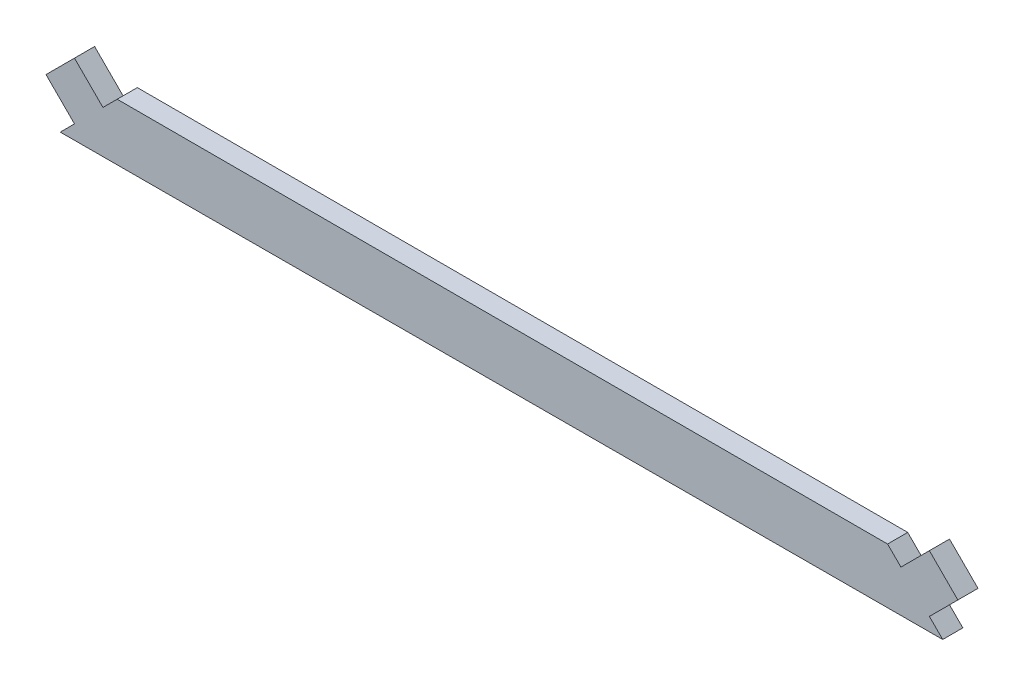
SolidWorks part; units mm, degrees
ref_plane "Front Plane" through (0, 0, 0) normal (0, 0, 1) x (1, 0, 0)
ref_plane "Top Plane" through (0, 0, 0) normal (0, 1, 0) x (1, 0, 0)
ref_plane "Right Plane" through (0, 0, 0) normal (1, 0, 0) x (0, 0, -1)
sketch "Sketch1" plane through (0, 0, 0) normal (0, 0, 1) x (1, 0, 0)
  line L0 (-139.4438, -165.8849) -> (138.8703, -165.3114)
  line L1 (0, -26.4411) -> (139.4438, -165.8849) construction
  line L2 (138.8703, -165.3114) -> (121.4833, -147.9244)
  line L3 (121.4833, -147.9244) -> (-121.4833, -147.9244)
  line L4 (-139.4438, -165.8849) -> (0, -26.4411) construction
  line L5 (-121.4833, -147.9244) -> (-139.4438, -165.8849)
  arc A0 (-204.2885, 69.85) -> (-138.8703, -165.3114) centre (0, 0) ccw construction
  dimension "D1" = 25.4
extrude "Boss-Extrude1" add sketch "Sketch1" along normal mid plane 6.35
sketch "Sketch2" plane through (0, 0, -3.175) normal (0, 0, -1) x (-1, 0, 0)
  line L0 (-130.1768, -156.6179) -> (-127.0422, -159.7525) construction
  line L1 (-138.8703, -165.3114) -> (-121.4833, -147.9244) construction
  line L2 (-125.6867, -152.1278) -> (-134.6669, -143.1475)
  line L3 (-134.6669, -143.1475) -> (-143.6472, -152.1278)
  line L4 (-143.6472, -152.1278) -> (-134.6669, -161.108)
  line L8 (-121.4833, -147.9244) -> (-125.6867, -152.1278)
  line L12 (139.4438, -165.8849) -> (121.4833, -147.9244)
  line L13 (121.4833, -147.9244) -> (-121.4833, -147.9244)
  line L14 (-121.4833, -147.9244) -> (-138.8703, -165.3114)
  line L15 (-138.8703, -165.3114) -> (139.4438, -165.8849)
  line L16 (139.4438, -165.8849) -> (121.4833, -147.9244)
  line L17 (121.4833, -147.9244) -> (-121.4833, -147.9244)
  line L18 (-134.6669, -161.108) -> (-138.8703, -165.3114)
  line L19 (-138.8703, -165.3114) -> (139.4438, -165.8849)
  dimension "D1" = 12.7
  dimension "D2" = 12.7
  dimension "D3" = 0
extrude "Boss-Extrude2" add sketch "Sketch2" against normal up to surface (6.35 mm away) up to face at (-0.1434, -156.7613, 3.175)
sketch "Sketch3" plane through (0, 0, -3.175) normal (0, 0, -1) x (-1, 0, 0)
  line L0 (130.4636, -156.9046) -> (137.1973, -150.1709) construction
  line L1 (121.4833, -147.9244) -> (139.4438, -165.8849) construction
  line L2 (125.9734, -152.4145) -> (134.9537, -143.4343)
  line L3 (134.9537, -143.4343) -> (143.9339, -152.4145)
  line L4 (143.9339, -152.4145) -> (134.9537, -161.3948)
  line L13 (139.4438, -165.8849) -> (121.4833, -147.9244)
  line L14 (121.4833, -147.9244) -> (-121.4833, -147.9244)
  line L15 (-121.4833, -147.9244) -> (-125.6867, -152.1278)
  line L16 (-125.6867, -152.1278) -> (-134.6669, -143.1475)
  line L17 (-134.6669, -143.1475) -> (-143.6472, -152.1278)
  line L18 (-143.6472, -152.1278) -> (-134.6669, -161.108)
  line L19 (-134.6669, -161.108) -> (-138.8703, -165.3114)
  line L20 (-138.8703, -165.3114) -> (139.4438, -165.8849)
  line L21 (134.9537, -161.3948) -> (125.9734, -152.4145)
  dimension "D1" = 12.7
  dimension "D2" = 12.7
  dimension "D3" = 0
extrude "Boss-Extrude4" add sketch "Sketch3" against normal blind 6.35
